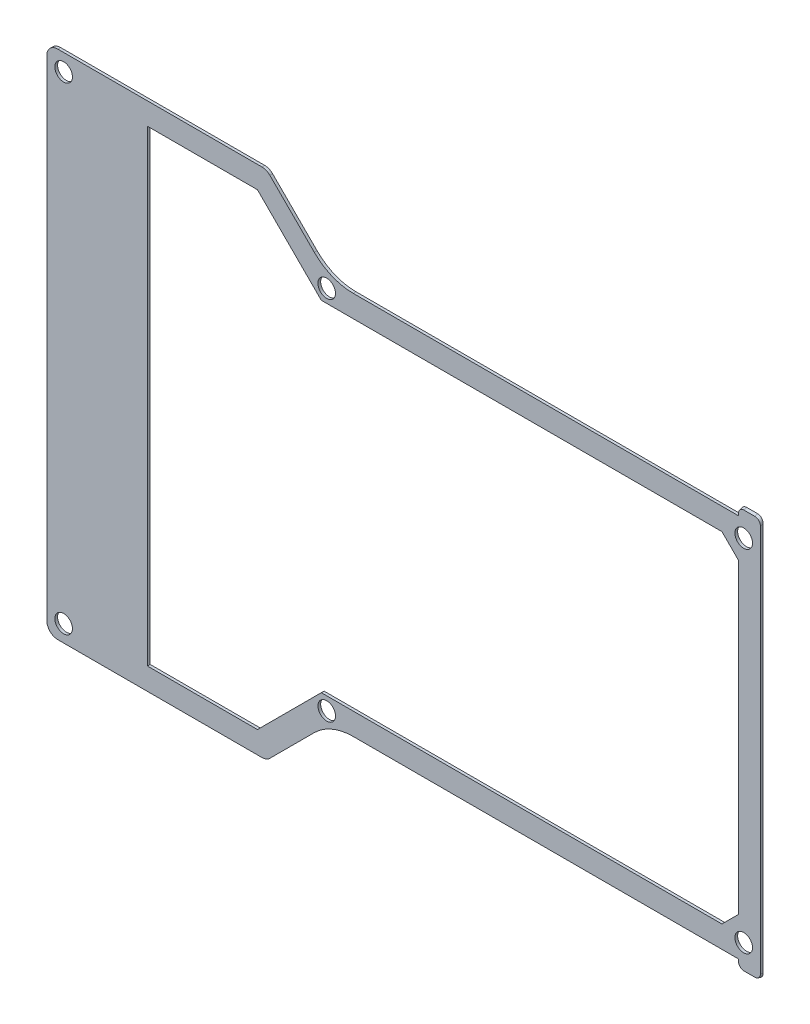
SolidWorks part; units mm, degrees
ref_plane "Front Plane" through (0, 0, 0) normal (0, 0, 1) x (1, 0, 0)
ref_plane "Top Plane" through (0, 0, 0) normal (0, 1, 0) x (1, 0, 0)
ref_plane "Right Plane" through (0, 0, 0) normal (1, 0, 0) x (0, 0, -1)
sketch "Sketch1" plane through (0, 0, 0) normal (0, 0, 1) x (1, 0, 0)
  line L0 (20, -100.2696) -> (0, -100.2696) construction
  line L1 (31.61, -88.6596) -> (20, -100.2696) construction
  line L2 (104.455, -88.6596) -> (31.61, -88.6596) construction
  line L3 (104.455, -88.6596) -> (107.455, -85.6596) construction
  line L4 (107.455, -29.8746) -> (107.455, -85.6596) construction
  line L5 (104.455, -26.8746) -> (107.455, -29.8746) construction
  line L6 (31.605, -26.8746) -> (104.455, -26.8746) construction
  line L7 (20, -15.2696) -> (31.605, -26.8746) construction
  line L8 (0, -100.2696) -> (0, -15.2696) construction
  line L9 (0, -15.2696) -> (20, -15.2696) construction
  line L10 (30.3329, -19.9457) -> (22.2426, -11.8554) construction
  line L11 (107.455, -22.8746) -> (37.404, -22.8746) construction
  line L12 (108.455, -21.3054) -> (110.455, -21.3054) construction
  line L15 (37.409, -92.6596) -> (107.455, -92.6596) construction
  line L16 (22.2426, -103.6838) -> (30.3379, -95.5885) construction
  line L17 (-16.3, -104.2696) -> (20.8284, -104.2696) construction
  line L18 (-18.3, -13.2696) -> (-18.3, -102.2696) construction
  line L19 (20.8284, -11.2696) -> (-16.3, -11.2696) construction
  line L20 (20, -100.2696) -> (0, -100.2696)
  line L21 (31.61, -88.6596) -> (20, -100.2696)
  line L22 (104.455, -88.6596) -> (31.61, -88.6596)
  line L23 (104.455, -88.6596) -> (107.455, -85.6596)
  line L24 (107.455, -29.8746) -> (107.455, -85.6596)
  line L25 (104.455, -26.8746) -> (107.455, -29.8746)
  line L26 (31.605, -26.8746) -> (104.455, -26.8746)
  line L27 (20, -15.2696) -> (31.605, -26.8746)
  line L28 (0, -100.2696) -> (0, -15.2696)
  line L29 (0, -15.2696) -> (20, -15.2696)
  line L30 (30.3329, -19.9457) -> (22.2426, -11.8554)
  line L31 (107.455, -22.8746) -> (37.404, -22.8746)
  line L32 (108.455, -21.3054) -> (110.455, -21.3054)
  line L33 (107.455, -94.2295) -> (111.455, -94.2295)
  line L34 (111.455, -94.2295) -> (111.455, -21.3054)
  line L35 (37.409, -92.6596) -> (107.455, -92.6596)
  line L36 (22.2426, -103.6838) -> (30.3379, -95.5885)
  line L37 (-16.3, -104.2696) -> (20.8284, -104.2696)
  line L38 (-18.3, -13.2696) -> (-18.3, -102.2696)
  line L39 (20.8284, -11.2696) -> (-16.3, -11.2696)
  line L40 (111.455, -21.3054) -> (107.455, -21.3054)
  line L41 (107.455, -94.2295) -> (107.455, -92.6596)
  line L42 (107.455, -21.3054) -> (107.455, -22.8746)
  arc A0 (22.2426, -11.8554) -> (20.8284, -11.2696) centre (20.8284, -13.2696) ccw construction
  arc A1 (30.3329, -19.9457) -> (37.404, -22.8746) centre (37.404, -12.8746) ccw construction
  arc A2 (37.409, -92.6596) -> (30.3379, -95.5885) centre (37.409, -102.6596) ccw construction
  arc A3 (20.8284, -104.2696) -> (22.2426, -103.6838) centre (20.8284, -102.2696) ccw construction
  arc A4 (-18.3, -102.2696) -> (-16.3, -104.2696) centre (-16.3, -102.2696) ccw construction
  arc A5 (-16.3, -11.2696) -> (-18.3, -13.2696) centre (-16.3, -13.2696) ccw construction
  arc A6 (22.2426, -11.8554) -> (20.8284, -11.2696) centre (20.8284, -13.2696) ccw
  arc A7 (30.3329, -19.9457) -> (37.404, -22.8746) centre (37.404, -12.8746) ccw
  arc A8 (37.409, -92.6596) -> (30.3379, -95.5885) centre (37.409, -102.6596) ccw
  arc A9 (20.8284, -104.2696) -> (22.2426, -103.6838) centre (20.8284, -102.2696) ccw
  arc A10 (-18.3, -102.2696) -> (-16.3, -104.2696) centre (-16.3, -102.2696) ccw
  arc A11 (-16.3, -11.2696) -> (-18.3, -13.2696) centre (-16.3, -13.2696) ccw
  circle A12 centre (108.4121, -25.9175) radius 1.25 construction
  circle A13 centre (32.5911, -24.494) radius 1.25 construction
  circle A14 centre (-15.2393, -14.3303) radius 1.25 construction
  circle A15 centre (-15.2393, -101.2089) radius 1.25 construction
  circle A16 centre (32.5961, -91.0402) radius 1.25 construction
  circle A17 centre (108.4121, -89.6167) radius 1.25 construction
  circle A18 centre (108.4121, -25.9175) radius 1.25 construction
  circle A19 centre (32.5911, -24.494) radius 1.25 construction
  circle A20 centre (-15.2393, -14.3303) radius 1.25 construction
  circle A21 centre (-15.2393, -101.2089) radius 1.25 construction
  circle A22 centre (32.5961, -91.0402) radius 1.25 construction
  circle A23 centre (108.4121, -89.6167) radius 1.25 construction
  circle A24 centre (-15.2393, -101.2089) radius 1.6
  circle A25 centre (32.5961, -91.0402) radius 1.6
  circle A26 centre (108.4121, -89.6167) radius 1.6
  circle A27 centre (108.4121, -25.9175) radius 1.6
  circle A28 centre (32.5911, -24.494) radius 1.6
  circle A29 centre (-15.2393, -14.3303) radius 1.6
extrude "Boss-Extrude1" add sketch "Sketch1" along normal blind 0.5 contours L39 A11 L38 A10 L37 A9 L36 A8 L35 L41 L33 L34 L40 L32 L42 L31 A7 L30 A6 A29 A28 A27 A26 A25 A24 L28 L29 L27 L26 L25 L24 L23 L22 L21 L20 region at (33.5161, -22.2609, 0)
sketch "Sketch2" plane through (111.455, 0, 0) normal (1, 0, 0) x (0, 0, -1)
  line L2 (28.78, -11.2696) -> (0, -21.3054)
  line L3 (0, -94.2295) -> (28.78, -104.2696)
  line L4 (0, -21.3054) -> (-2.5092, -22.1804)
  line L5 (-2.5092, -22.1804) -> (-2.2343, -18.9333)
  line L6 (-2.2343, -18.9333) -> (1.8663, -18.9333)
  line L7 (1.8663, -18.9333) -> (0, -21.3054)
  line L8 (0, -94.2295) -> (-3.7144, -92.9337)
  line L9 (-3.7144, -92.9337) -> (-3.7144, -98.6628)
  line L10 (-3.7144, -98.6628) -> (4.2666, -98.6628)
  line L11 (4.2666, -98.6628) -> (0, -94.2295)
extrude "Cut-Extrude3" cut sketch "Sketch2" against normal blind 10 contours L10 L11 L8 L9 | L7 L6 L5 L4 | L4 | L8 region at (111.455, -20.2093, 0.7767) region at (111.455, -96.4678, 0.815)
fillet "Fillet1" radius 1 4 edges at (107.455, -94.1422, 0.25) (111.455, -94.1422, 0.25) (107.455, -21.3926, 0.25) (111.455, -21.3926, 0.25)
